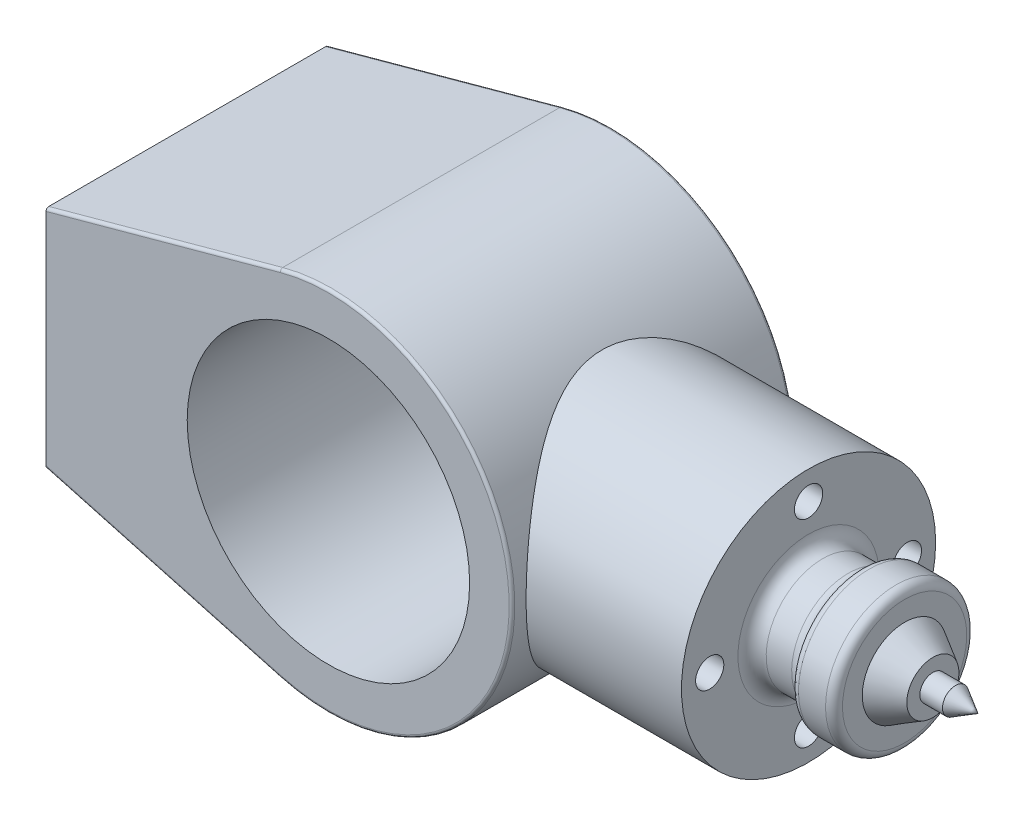
SolidWorks part; units mm, degrees
ref_plane "Front Plane" through (0, 0, 0) normal (0, 0, 1) x (1, 0, 0)
ref_plane "Top Plane" through (0, 0, 0) normal (0, 1, 0) x (1, 0, 0)
ref_plane "Right Plane" through (0, 0, 0) normal (1, 0, 0) x (0, 0, -1)
sketch "Sketch1" plane through (0, 0, 0) normal (0, 0, 1) x (1, 0, 0)
  line L0 (0, 0) -> (-100, 0) construction
  line L1 (-100, -40) -> (-100, 40)
  line L2 (-100, 40) -> (-17.1739, 62.6902)
  line L3 (-100, -40) -> (-17.1739, -62.6902)
  arc A0 (-17.1739, -62.6902) -> (-17.1739, 62.6902) centre (0, 0) ccw
  circle A1 centre (0, 0) radius 50
  dimension "D1" = 100
  dimension "D2" = 130
  dimension "D3" = 100
  dimension "D4" = 80
extrude "Boss-Extrude1" add sketch "Sketch1" along normal mid plane 100
sketch "Sketch2" plane through (0, 0, 0) normal (1, 0, 0) x (0, 0, -1)
  circle A0 centre (0, 0) radius 45
  dimension "D1" = 90
extrude "Boss-Extrude2" add sketch "Sketch2" against normal up to next from offset 120
sketch "Sketch3" plane through (0, 0, 0) normal (0, 0, 1) x (1, 0, 0)
  line L0 (120, 0) -> (180, 0)
  line L2 (120, -45) -> (120, 45) construction
  line L3 (180, 0) -> (172.0192, -4.6077)
  line L4 (172.0192, -4.6077) -> (164.0192, -4.6077)
  line L5 (164.0192, -4.6077) -> (164.0192, -9.2265)
  line L6 (164.0192, -9.2265) -> (154.0192, -15)
  line L7 (154.0192, -15) -> (154.0192, -25)
  line L8 (154.0192, -25) -> (139.0192, -25)
  line L9 (139.0192, -25) -> (139.0192, -20)
  line L10 (139.0192, -20) -> (120, -20)
  line L11 (0, 0) -> (120, 0) construction
  line L12 (120, 0) -> (120, -20)
  dimension "D1" = 60
  dimension "D2" = 8
  dimension "D3" = 10
  dimension "D4" = 15
  dimension "D5" = 10
  dimension "D6" = 5
  dimension "D7" = 20
  dimension "120" = 120
revolve "Revolve1" add sketch "Sketch3" angle 360 about L11
sketch "Sketch4" plane through (120, 0, 0) normal (1, 0, 0) x (0, 0, -1)
  circle A0 centre (0, 0) radius 35 construction
  circle A1 centre (0, 35) radius 5
  circle A2 centre (35, 0) radius 5
  circle A3 centre (0, -35) radius 5
  circle A4 centre (-35, 0) radius 5
  point P5 (0, 0)
  point P6 (0, 0)
  point P7 (0, 0)
  point P14 (0, 0)
  point P15 (0, 0)
  dimension "D1" = 70
  dimension "D2" = 10
  dimension "D3" = 4
extrude "Cut-Extrude1" cut sketch "Sketch4" against normal blind 20
fillet "Fillet1" radius 5 2 edges at (139.0192, -20, 0) (120, -20, 0)
fillet "Fillet2" radius 1 6 edges at (-58.587, -51.3451, -50) (65, 0, -50) (-58.587, -51.3451, 50) (65, 0, 50) (-58.587, 51.3451, -50) (-58.587, 51.3451, 50)
fillet "Fillet3" radius 3 2 edges at (139.0192, -25, 0) (154.0192, -25, 0)
